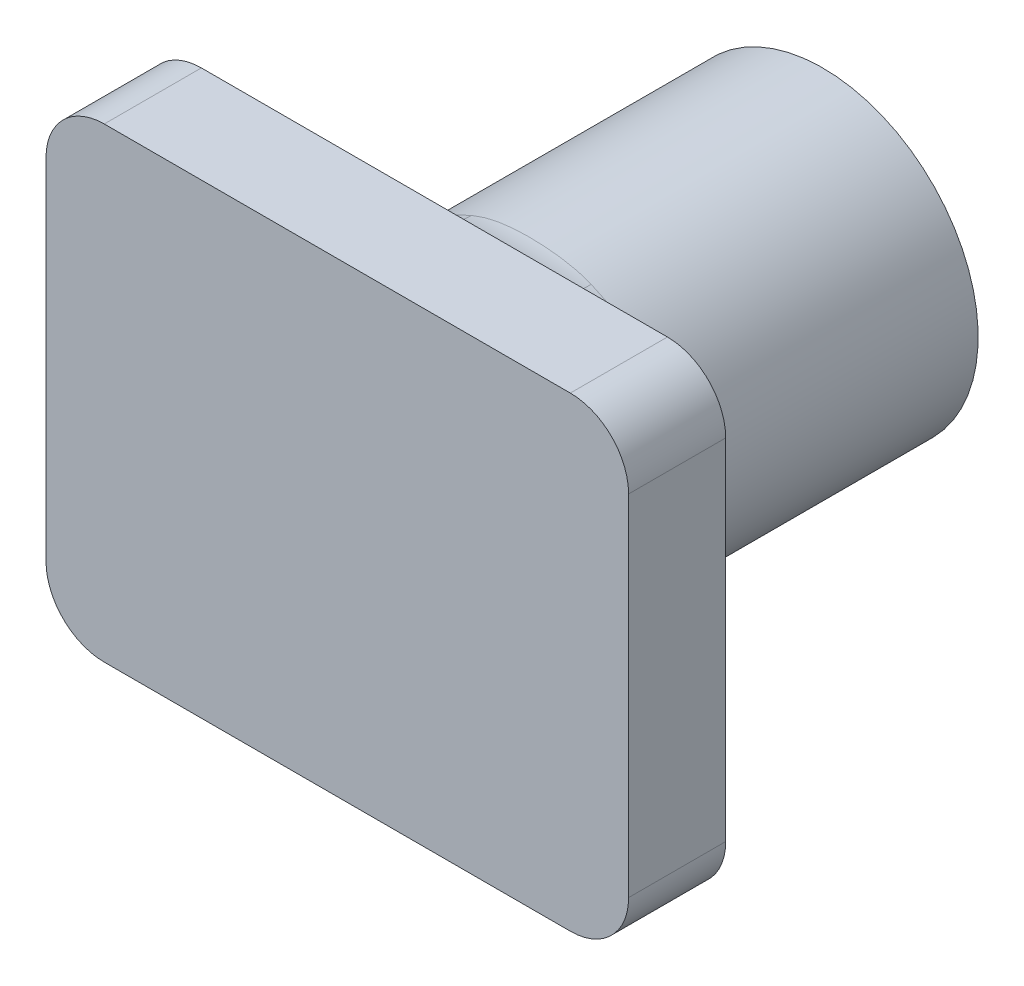
SolidWorks part; units mm, degrees
ref_plane "Front Plane" through (0, 0, 0) normal (0, 0, 1) x (1, 0, 0)
ref_plane "Top Plane" through (0, 0, 0) normal (0, 1, 0) x (1, 0, 0)
ref_plane "Right Plane" through (0, 0, 0) normal (1, 0, 0) x (0, 0, -1)
sketch "Sketch1" plane through (0, 0, 0) normal (0, 0, 1) x (1, 0, 0)
  line L1 (-15, -12) -> (15, -12)
  line L2 (-15, -12) -> (-15, 12)
  line L3 (-15, 12) -> (15, 12)
  line L4 (15, -12) -> (15, 12)
  line L5 (-15, -12) -> (15, 12) construction
  line L6 (-15, 12) -> (15, -12) construction
  point P0 (0, 0)
  dimension "D1" = 30
  dimension "D2" = 24
extrude "Boss-Extrude1" add sketch "Sketch1" along normal blind 5
sketch "Sketch3" plane through (0, 0, 0) normal (0, 0, -1) x (-1, 0, 0)
  circle A0 centre (0, 0) radius 8
  circle A1 centre (0, 0) radius 5.1
extrude "Boss-Extrude3" add sketch "Sketch3" along normal blind 20
fillet "Fillet5" radius 3 4 edges at (-15, 12, 2.5) (-15, -12, 2.5) (15, -12, 2.5) (15, 12, 2.5)
fillet "Fillet6" radius 5 1 edges at (-8, 0, 0)
